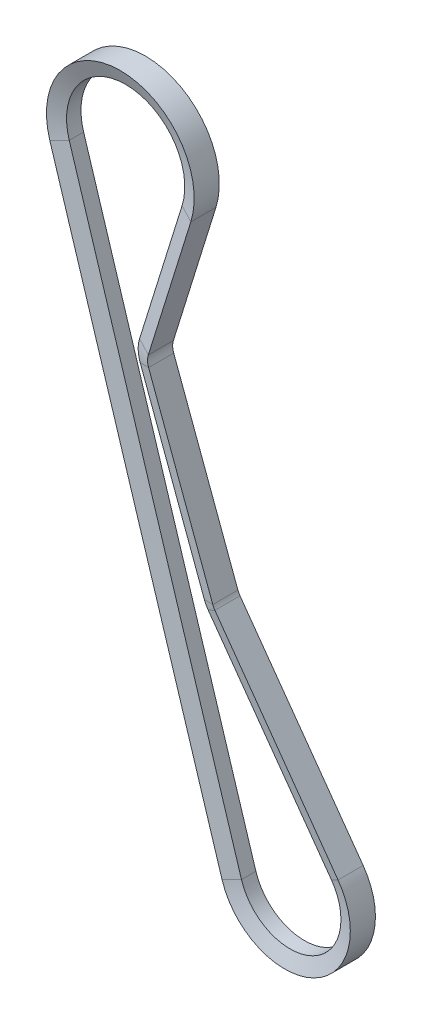
SolidWorks part; units mm, degrees
ref_plane "Front Plane" through (0, 0, 0) normal (0, 0, 1) x (1, 0, 0)
ref_plane "Top Plane" through (0, 0, 0) normal (0, 1, 0) x (1, 0, 0)
ref_plane "Right Plane" through (0, 0, 0) normal (1, 0, 0) x (0, 0, -1)
sketch "Sketch2" plane through (0, 0, 0) normal (0, 0, 1) x (1, 0, 0)
  line L0 (0, 0) -> (1, 0) construction
  line L1 (0, 0) -> (0, 1) construction
  line L12 (-23.7534, -7.3853) -> (-89.0636, 202.6738)
  line L14 (-35.5932, 202.6594) -> (-51.717, 150.8984)
  line L15 (-51.6082, 146.8021) -> (-27.2713, 81.169)
  line L16 (-26.4796, 79.6787) -> (20.2218, 14.486)
  arc A4 (-89.0636, 202.6738) -> (-35.5932, 202.6594) centre (-62.3262, 210.9868) cw
  arc A7 (20.2218, 14.486) -> (-23.7534, -7.3853) centre (0, 0) cw
  arc A8 (-51.717, 150.8984) -> (-51.6082, 146.8021) centre (-45.6544, 149.0099) ccw
  arc A9 (-27.2713, 81.169) -> (-26.4796, 79.6787) centre (-21.3174, 83.3767) ccw
ref_plane "Plane4" through (20.2218, 14.486, 0) normal (0.5824, -0.8129, 0) x (-0.8129, -0.5824, 0)
sketch "Sketch3" plane through (20.2218, 14.486, 0) normal (0.5824, -0.8129, 0) x (-0.8129, -0.5824, 0)
  line L0 (0, -4.7625) -> (0, 4.7625)
  line L1 (0, -4.7625) -> (5.588, -2.7286)
  line L2 (5.588, -2.7286) -> (5.588, 2.7286)
  line L3 (5.588, 2.7286) -> (0, 4.7625)
  line L4 (0, 0) -> (5.588, 0) construction
  dimension "D1" = 9.525
  dimension "D2" = 5.588
  dimension "D3" = 40
sweep "Sweep1" add profiles "Sketch3" path "Sketch2"
